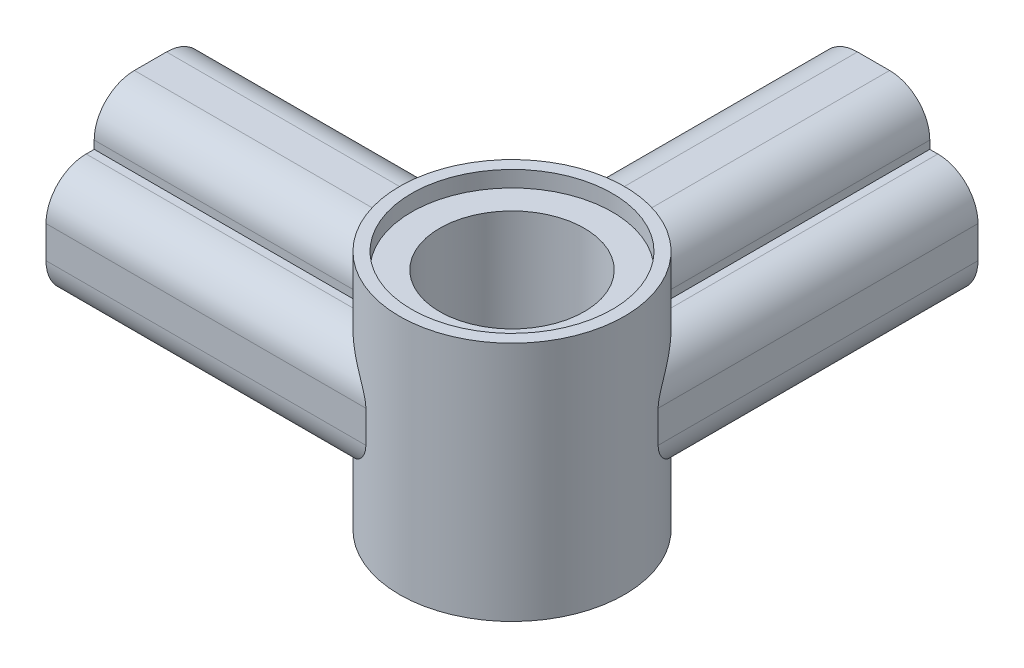
SolidWorks part; units mm, degrees
material "ABS PC"
ref_plane "Front Plane" through (0, 0, 0) normal (0, 0, 1) x (1, 0, 0)
ref_plane "Top Plane" through (0, 0, 0) normal (0, 1, 0) x (1, 0, 0)
ref_plane "Right Plane" through (0, 0, 0) normal (1, 0, 0) x (0, 0, -1)
sketch "Sketch1" plane through (0, 0, 0) normal (0, 0, 1) x (1, 0, 0)
  line L0 (-0.762, 2.032) -> (-0.762, 1.016)
  line L1 (-1.016, 0.762) -> (-2.032, 0.762)
  line L2 (-2.286, 0.508) -> (-2.286, -0.508)
  line L3 (-2.032, -0.762) -> (-1.016, -0.762)
  line L4 (-0.762, -1.016) -> (-0.762, -2.032)
  line L5 (-0.508, -2.286) -> (0.508, -2.286)
  line L6 (0.762, -2.032) -> (0.762, -1.016)
  line L7 (1.016, -0.762) -> (2.032, -0.762)
  line L8 (2.286, -0.508) -> (2.286, 0.508)
  line L9 (2.032, 0.762) -> (1.016, 0.762)
  line L10 (0.762, 1.016) -> (0.762, 2.032)
  line L11 (0.508, 2.286) -> (-0.508, 2.286)
  line L12 (0, -22.3743) -> (0, 22.3743) construction
  line L13 (39.1001, 0) -> (-39.1001, 0) construction
  line L14 (2.032, 1.778) -> (1.778, 1.778)
  line L15 (1.778, 1.778) -> (1.778, 2.032)
  line L16 (0.508, 3.302) -> (-0.508, 3.302)
  line L17 (-1.778, 2.032) -> (-1.778, 1.778)
  line L18 (-1.778, 1.778) -> (-2.032, 1.778)
  line L19 (-3.302, 0.508) -> (-3.302, -0.508)
  line L20 (-2.032, -1.778) -> (-1.778, -1.778)
  line L21 (-1.778, -1.778) -> (-1.778, -2.032)
  line L22 (-0.508, -3.302) -> (0.508, -3.302)
  line L23 (1.778, -2.032) -> (1.778, -1.778)
  line L24 (1.778, -1.778) -> (2.032, -1.778)
  line L25 (3.302, -0.508) -> (3.302, 0.508)
  arc A0 (-0.762, 1.016) -> (-1.016, 0.762) centre (-1.016, 1.016) cw
  arc A1 (-0.762, 2.032) -> (-0.508, 2.286) centre (-0.508, 2.032) cw
  arc A2 (0.508, 2.286) -> (0.762, 2.032) centre (0.508, 2.032) cw
  arc A3 (0.762, 1.016) -> (1.016, 0.762) centre (1.016, 1.016) ccw
  arc A4 (2.032, 0.762) -> (2.286, 0.508) centre (2.032, 0.508) cw
  arc A5 (2.032, -0.762) -> (2.286, -0.508) centre (2.032, -0.508) ccw
  arc A6 (1.016, -0.762) -> (0.762, -1.016) centre (1.016, -1.016) ccw
  arc A7 (0.762, -2.032) -> (0.508, -2.286) centre (0.508, -2.032) cw
  arc A8 (-0.508, -2.286) -> (-0.762, -2.032) centre (-0.508, -2.032) cw
  arc A9 (-1.016, -0.762) -> (-0.762, -1.016) centre (-1.016, -1.016) cw
  arc A10 (-2.032, -0.762) -> (-2.286, -0.508) centre (-2.032, -0.508) cw
  arc A11 (-2.286, 0.508) -> (-2.032, 0.762) centre (-2.032, 0.508) cw
  arc A12 (1.778, 1.778) -> (1.778, 1.778) centre (1.778, 1.778) ccw
  arc A13 (0.508, 3.302) -> (1.778, 2.032) centre (0.508, 2.032) cw
  arc A14 (-1.778, 2.032) -> (-0.508, 3.302) centre (-0.508, 2.032) cw
  arc A15 (-1.778, 1.778) -> (-1.778, 1.778) centre (-1.778, 1.778) cw
  arc A16 (-3.302, 0.508) -> (-2.032, 1.778) centre (-2.032, 0.508) cw
  arc A17 (-2.032, -1.778) -> (-3.302, -0.508) centre (-2.032, -0.508) cw
  arc A18 (-1.778, -1.778) -> (-1.778, -1.778) centre (-1.778, -1.778) cw
  arc A19 (-0.508, -3.302) -> (-1.778, -2.032) centre (-0.508, -2.032) cw
  arc A20 (1.778, -2.032) -> (0.508, -3.302) centre (0.508, -2.032) cw
  arc A21 (1.778, -1.778) -> (1.778, -1.778) centre (1.778, -1.778) ccw
  arc A22 (2.032, -1.778) -> (3.302, -0.508) centre (2.032, -0.508) ccw
  arc A23 (2.032, 1.778) -> (3.302, 0.508) centre (2.032, 0.508) cw
  point P40 (0, 0)
  dimension "D6" = 0.254
  dimension "D7" = 1.016
  dimension "D1" = 4.572
  dimension "D2" = 4.572
  dimension "D3" = 1.524
  dimension "D4" = 1.524
  dimension "D5" = 1.524
extrude "Extrude1" add sketch "Sketch1" along normal blind 11.43
sketch "Sketch4" plane through (0, 0, 0) normal (1, 0, 0) x (0, 0, -1)
  line L0 (-11.43, 6.9061) -> (-11.43, -5.9011)
  dimension "D1" = 11.43
ref_axis "Axis1" through (0, -5.9011, 11.43) along (0, 1, 0)
pattern_circular "CirPattern1" count 2 every 90 about axis through (0, -5.9011, 11.43) along (0, 1, 0) of "Extrude1"
sketch "Sketch6" plane through (0, 0, 0) normal (0, 1, 0) x (1, 0, 0)
  circle A0 centre (0, -11.43) radius 3.556
  dimension "D1" = 7.112
extrude "Extrude2" add sketch "Sketch6" along normal mid plane 7.62
sketch "Sketch7" plane through (0, 3.81, 0) normal (0, 1, 0) x (1, 0, 0)
  circle A0 centre (0, -11.43) radius 3.175
  dimension "D1" = 6.35
extrude "Cut-Extrude2" cut sketch "Sketch7" against normal blind 0.508
mirror "Mirror1" about plane through (0, 0, 0) normal (0, 1, 0) of "Cut-Extrude2"
sketch "Sketch8" plane through (0, 3.302, 0) normal (0, 1, 0) x (1, 0, 0)
  circle A0 centre (0, -11.43) radius 2.286
  dimension "D1" = 4.572
extrude "Cut-Extrude3" cut sketch "Sketch8" against normal through all
